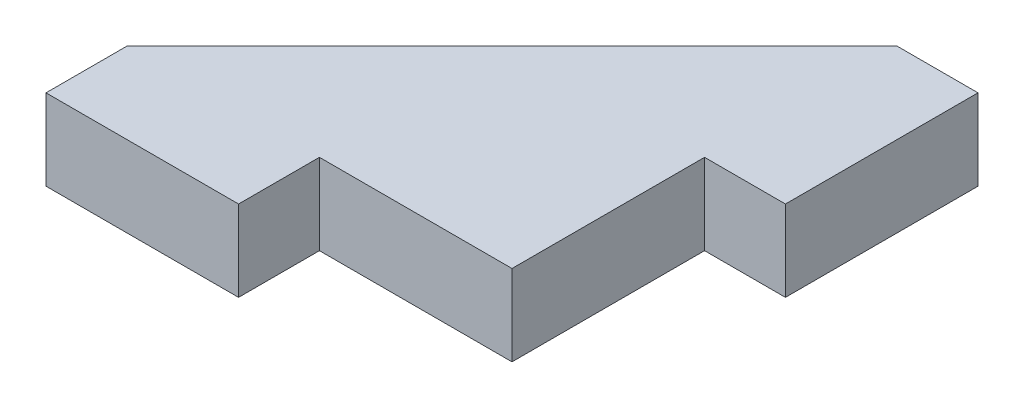
SolidWorks part; units mm, degrees
ref_plane "Front Plane" through (0, 0, 0) normal (0, 0, 1) x (1, 0, 0)
ref_plane "Top Plane" through (0, 0, 0) normal (0, 1, 0) x (1, 0, 0)
ref_plane "Right Plane" through (0, 0, 0) normal (1, 0, 0) x (0, 0, -1)
sketch "Sketch1" plane through (0, 0, 0) normal (0, 1, 0) x (1, 0, 0)
  line L0 (-21.062, -13.6221) -> (4.338, 11.7779)
  line L2 (4.338, 11.7779) -> (9.672, 11.7779)
  line L3 (-21.062, -13.6221) -> (4.338, -13.6221)
  line L4 (4.338, 11.7779) -> (4.338, -13.6221)
  line L5 (4.338, 11.7779) -> (4.338, -0.9221)
  line L6 (4.338, -0.9221) -> (9.672, -0.9221)
  line L7 (9.672, 11.7779) -> (9.672, -0.9221)
  line L8 (-21.062, -13.6221) -> (-8.362, -13.6221)
  line L9 (-21.062, -13.6221) -> (-21.062, -18.9561)
  line L10 (-21.062, -18.9561) -> (-8.362, -18.9561)
  line L11 (-8.362, -13.6221) -> (-8.362, -18.9561)
  dimension "D2" = 25.4
  dimension "D3" = 12.7
  dimension "D4" = 5.334
  dimension "D5" = 5.334
extrude "Boss-Extrude1" add sketch "Sketch1" along normal blind 5.334 contours L11 L3 L9 L10 | L4 L0 L3 | L7 L2 L4 L6 region at (-4.1287, 0, 5.1554) region at (-14.712, 0, 16.2891) region at (7.005, 0, -5.4279)
equation "\"MDF\"= .21in"
equation "\"Foamcore\"= .13in"
equation "\"Gmaterial\"= \"MDF\""
equation "\"D4@Sketch1\"=\"MDF\""
equation "\"D5@Sketch1\"=\"MDF\""
equation "\"D1@Boss-Extrude1\"=\"MDF\""
